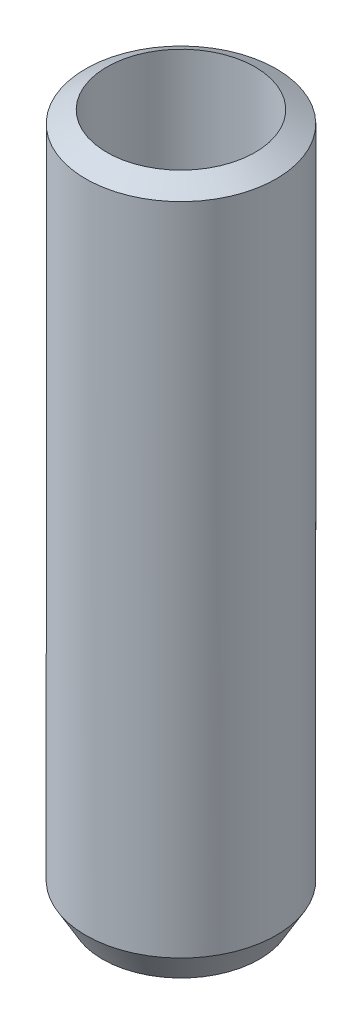
SolidWorks part; units mm, degrees
ref_plane "Front Plane" through (0, 0, 0) normal (0, 0, 1) x (1, 0, 0)
ref_plane "Top Plane" through (0, 0, 0) normal (0, 1, 0) x (1, 0, 0)
ref_plane "Right Plane" through (0, 0, 0) normal (1, 0, 0) x (0, 0, -1)
sketch "Sketch1" plane through (0, 0, 0) normal (0, 1, 0) x (1, 0, 0)
  circle A0 centre (0, 0) radius 27.5
  dimension "SHAFT_OD" = 55
extrude "Boss-Extrude1" add sketch "Sketch1" along normal blind 202.2972
sketch "Sketch2" plane through (0, 0, 0) normal (0, 1, 0) x (1, 0, 0)
  circle A0 centre (0, 0) radius 21.3774
  dimension "BORE_D" = 42.7549
extrude "Cut-Extrude1" cut sketch "Sketch2" along normal through all
chamfer "Chamfer1" distance 4.8653 angle 60 2 edges at (0, 202.2972, 27.5) (0, 0, 27.5) first distance on face at (0, 202.2972, 27.5) first distance on face at (0, 0, 21.3774)
